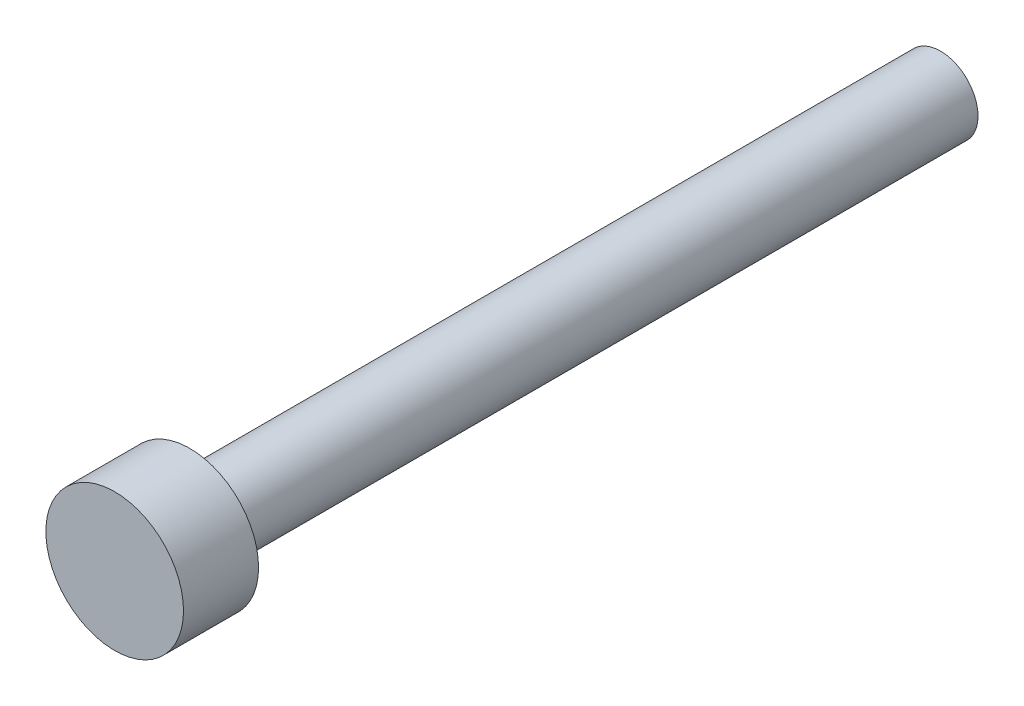
SolidWorks part; units mm, degrees
ref_plane "Front Plane" through (0, 0, 0) normal (0, 0, 1) x (1, 0, 0)
ref_plane "Top Plane" through (0, 0, 0) normal (0, 1, 0) x (1, 0, 0)
ref_plane "Right Plane" through (0, 0, 0) normal (1, 0, 0) x (0, 0, -1)
sketch "Shank_nominal_thread_envelope_profile" plane through (0, 0, 0) normal (0, 0, 1) x (1, 0, 0)
  circle A0 centre (0, 0) radius 1.5
  dimension "D1" = 3
extrude "Shank_nominal_thread_envelope" add sketch "Shank_nominal_thread_envelope_profile" along normal blind 30 from offset 30 offset against normal yes
sketch "Socket_head_envelope_profile" plane through (0, 0, 0) normal (0, 0, 1) x (1, 0, 0)
  circle A0 centre (0, 0) radius 2.75
  dimension "D1" = 5.5
extrude "Socket_head_envelope" add sketch "Socket_head_envelope_profile" along normal blind 3
